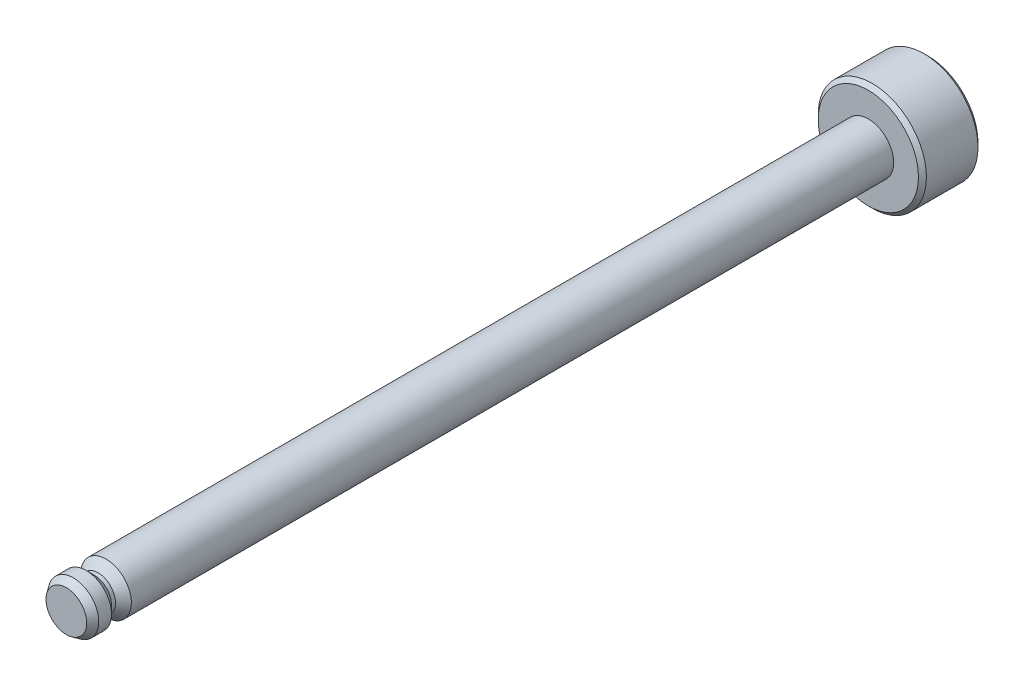
SolidWorks part; units mm, degrees
ref_plane "Front" through (0, 0, 0) normal (0, 0, 1) x (1, 0, 0)
ref_plane "Top" through (0, 0, 0) normal (0, 1, 0) x (1, 0, 0)
ref_plane "Right" through (0, 0, 0) normal (1, 0, 0) x (0, 0, -1)
sketch "Sketch2" plane through (0, 0, 0) normal (0, 0, 1) x (1, 0, 0)
  circle A0 centre (0, 0) radius 1.275
  dimension "D1" = 2.55
extrude "Shaft" add sketch "Sketch2" along normal blind 40.4
sketch "Sketch5" plane through (0, 0, 0) normal (0, 0, 1) x (1, 0, 0)
  circle A0 centre (0, 0) radius 2.725
  dimension "D1" = 5.45
extrude "Head" add sketch "Sketch5" against normal blind 3
chamfer "Chamfer1" distance 0.25 angle 55 1 edges at (1.275, 0, 40.4) first distance on face at (1.275, 0, 40.4)
chamfer "Deburs" distance 0.2 angle 45 2 edges at (2.725, 0, 0) (2.725, 0, -3)
sketch "Sketch6" plane through (0, 0, 0) normal (1, 0, 0) x (0, 0, -1)
  line L0 (0, 0) -> (-38.9, 0) construction
  line L1 (-38.9, 0) -> (-38.9, 0.875) construction
  line L2 (0, 1.275) -> (-40.043, 1.275) construction
  line L3 (-39.4, 1.275) -> (-38.4, 1.275)
  line L4 (-38.4, 1.275) -> (-38.8, 0.875)
  line L5 (-38.8, 0.875) -> (-39, 0.875)
  line L6 (-39, 0.875) -> (-39.4, 1.275)
  line L7 (-38.9, 0.875) -> (-38.9, 1.275) construction
  dimension "D1" = 38.9
  dimension "D2" = 0.4
  dimension "D3" = 1
revolve "e-Clip Notch Long" cut sketch "Sketch6" angle 360 about L0
equation "\"D1@Sketch2\"=\"Plastic Hardware OD@Box Assy.Assembly\""
equation "\"D1\"= \"Countersink Diameter@Box Assy.Assembly\" - .3mm"
equation "\"D1@Head\"=\"Countersink Depth@Box Assy.Assembly\""
equation "\"Length\"= 40mm"
equation "\"D1@Shaft\"=\"Length\"+.4mm"
equation "\"D1@Sketch6\"=\"Length\"-1.1mm"
